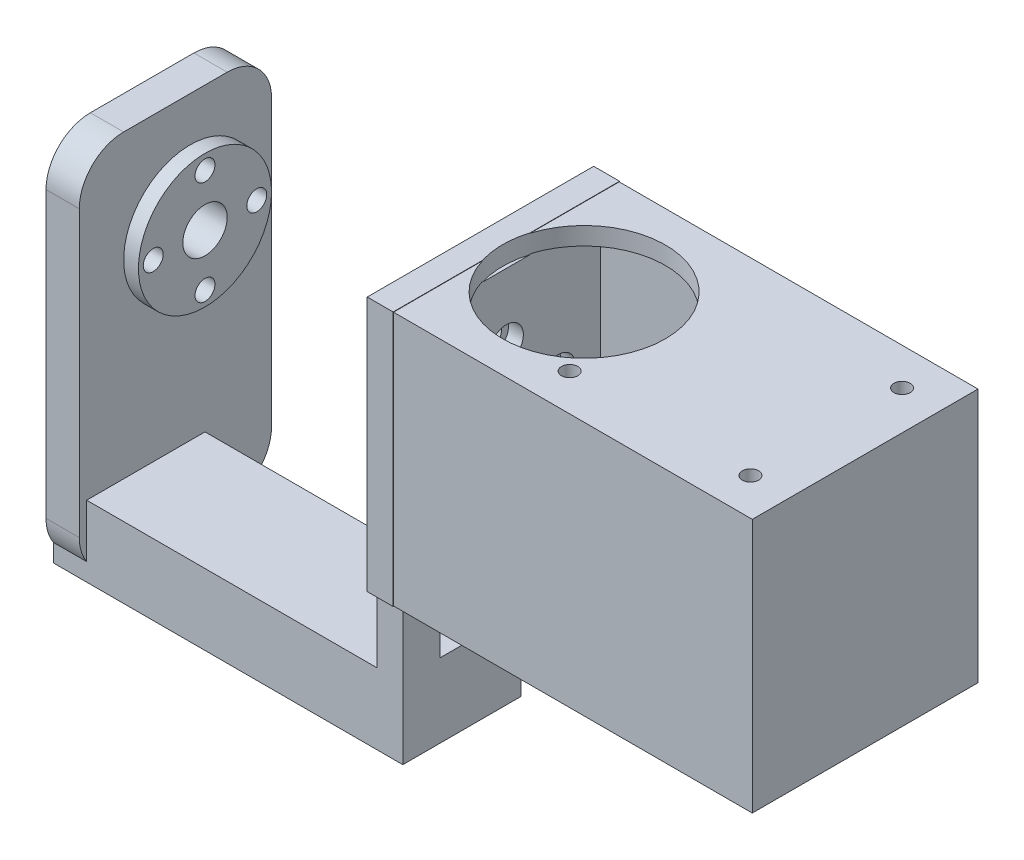
SolidWorks part; units mm, degrees
ref_plane "Front Plane" through (0, 0, 0) normal (0, 0, 1) x (1, 0, 0)
ref_plane "Top Plane" through (0, 0, 0) normal (0, 1, 0) x (1, 0, 0)
ref_plane "Right Plane" through (0, 0, 0) normal (1, 0, 0) x (0, 0, -1)
ref_plane "PX_m14_010" through (-14.01, 0, 0) normal (1, 0, 0) x (0, 0, -1)
sketch "S_prism1" plane through (-14.01, 0, 0) normal (1, 0, 0) x (0, 0, -1)
  line L0 (15.31, 18.45) -> (15.31, -16.05)
  line L1 (15.31, -16.05) -> (-15.31, -16.05)
  line L2 (-15.31, -16.05) -> (-15.31, 18.45)
  line L3 (-15.31, 18.45) -> (15.31, 18.45)
extrude "Boss_1" add sketch "S_prism1" along normal blind 3.5
ref_plane "PX_m53_260" through (-53.26, 0, 0) normal (1, 0, 0) x (0, 0, -1)
sketch "S_cyl2" plane through (-53.26, 0, 0) normal (1, 0, 0) x (0, 0, -1)
  circle A0 centre (0, 0) radius 9
  dimension "D1_S_cyl2" = 18
extrude "Boss_2" add sketch "S_cyl2" along normal blind 2
ref_plane "PX_m57_760" through (-57.76, 0, 0) normal (1, 0, 0) x (0, 0, -1)
sketch "S_prism3" plane through (-57.76, 0, 0) normal (1, 0, 0) x (0, 0, -1)
  line L0 (11, 9) -> (11, -29.5)
  line L1 (5, -35.5) -> (-9, -35.5)
  line L2 (-15, -29.5) -> (-15, 9)
  line L3 (-9, 15) -> (5, 15)
  arc A0 (5, 15) -> (11, 9) centre (4.9999, 8.9999) cw
  arc A1 (11, -29.5) -> (5, -35.5) centre (4.9999, -29.4999) cw
  arc A2 (-9, -35.5) -> (-15, -29.5) centre (-8.9999, -29.4999) cw
  arc A3 (-15, 9) -> (-9, 15) centre (-8.9999, 8.9999) cw
extrude "Boss_3" add sketch "S_prism3" along normal blind 4.5
ref_plane "PZ_m15_260" through (0, 0, -15.26) normal (0, 0, 1) x (1, 0, 0)
sketch "S_box4" plane through (0, 0, -15.26) normal (0, 0, 1) x (1, 0, 0)
  line L0 (-13.01, -16) -> (-10.51, -16)
  line L1 (-10.51, -16) -> (-10.51, 18.4)
  line L2 (-10.51, 18.4) -> (-13.01, 18.4)
  line L3 (-13.01, 18.4) -> (-13.01, -16)
  dimension "P1" = 13.01
  dimension "P2" = 16
  dimension "P3" = 10.51
  dimension "P4" = 16
  dimension "P5" = 10.51
  dimension "P6" = 18.4
  dimension "P7" = 13.01
  dimension "P8" = 18.4
extrude "Boss_4" add sketch "S_box4" along normal blind 30.52
sketch "S_box5" plane through (0, 0, -15.26) normal (0, 0, 1) x (1, 0, 0)
  line L0 (35.51, -16) -> (38.01, -16)
  line L1 (38.01, -16) -> (38.01, 18.4)
  line L2 (38.01, 18.4) -> (35.51, 18.4)
  line L3 (35.51, 18.4) -> (35.51, -16)
  dimension "P1" = 35.51
  dimension "P2" = 16
  dimension "P3" = 38.01
  dimension "P4" = 16
  dimension "P5" = 38.01
  dimension "P6" = 18.4
  dimension "P7" = 35.51
  dimension "P8" = 18.4
extrude "Boss_5" add sketch "S_box5" along normal blind 30.52
sketch "S_box6" plane through (0, 0, -15.26) normal (0, 0, 1) x (1, 0, 0)
  line L0 (-13.01, -16) -> (38.01, -16)
  line L1 (38.01, -16) -> (38.01, 18.4)
  line L2 (38.01, 18.4) -> (-13.01, 18.4)
  line L3 (-13.01, 18.4) -> (-13.01, -16)
  dimension "P1" = 13.01
  dimension "P2" = 16
  dimension "P3" = 38.01
  dimension "P4" = 16
  dimension "P5" = 38.01
  dimension "P6" = 18.4
  dimension "P7" = 13.01
  dimension "P8" = 18.4
extrude "Boss_6" add sketch "S_box6" along normal blind 2.5
ref_plane "PZ_p12_760" through (0, 0, 12.76) normal (0, 0, 1) x (1, 0, 0)
sketch "S_box7" plane through (0, 0, 12.76) normal (0, 0, 1) x (1, 0, 0)
  line L0 (-13.01, -16) -> (38.01, -16)
  line L1 (38.01, -16) -> (38.01, 18.4)
  line L2 (38.01, 18.4) -> (-13.01, 18.4)
  line L3 (-13.01, 18.4) -> (-13.01, -16)
  dimension "P1" = 13.01
  dimension "P2" = 16
  dimension "P3" = 38.01
  dimension "P4" = 16
  dimension "P5" = 38.01
  dimension "P6" = 18.4
  dimension "P7" = 13.01
  dimension "P8" = 18.4
extrude "Boss_7" add sketch "S_box7" along normal blind 2.5
sketch "S_box8" plane through (0, 0, -15.26) normal (0, 0, 1) x (1, 0, 0)
  line L0 (-13.01, 16) -> (38.01, 16)
  line L1 (38.01, 16) -> (38.01, 18.4)
  line L2 (38.01, 18.4) -> (-13.01, 18.4)
  line L3 (-13.01, 18.4) -> (-13.01, 16)
  dimension "P1" = 13.01
  dimension "P2" = 16
  dimension "P3" = 38.01
  dimension "P4" = 16
  dimension "P5" = 38.01
  dimension "P6" = 18.4
  dimension "P7" = 13.01
  dimension "P8" = 18.4
extrude "Boss_8" add sketch "S_box8" along normal blind 30.52
ref_plane "PZ_p9_000" through (0, 0, 9) normal (0, 0, 1) x (1, 0, 0)
sketch "S_box9" plane through (0, 0, 9) normal (0, 0, 1) x (1, 0, 0)
  line L0 (-14.01, -25.725) -> (-10.51, -25.725)
  line L1 (-10.51, -25.725) -> (-10.51, -16)
  line L2 (-10.51, -16) -> (-14.01, -16)
  line L3 (-14.01, -16) -> (-14.01, -25.725)
  dimension "P1" = 14.01
  dimension "P2" = 25.725
  dimension "P3" = 10.51
  dimension "P4" = 25.725
  dimension "P5" = 10.51
  dimension "P6" = 16
  dimension "P7" = 14.01
  dimension "P8" = 16
extrude "Boss_9" add sketch "S_box9" along normal blind 5
ref_plane "PZ_m2_000" through (0, 0, -2) normal (0, 0, 1) x (1, 0, 0)
sketch "S_box10" plane through (0, 0, -2) normal (0, 0, 1) x (1, 0, 0)
  line L0 (-14.01, -35.225) -> (-10.51, -35.225)
  line L1 (-10.51, -35.225) -> (-10.51, -25.225)
  line L2 (-10.51, -25.225) -> (-14.01, -25.225)
  line L3 (-14.01, -25.225) -> (-14.01, -35.225)
  dimension "P1" = 14.01
  dimension "P2" = 35.225
  dimension "P3" = 10.51
  dimension "P4" = 35.225
  dimension "P5" = 10.51
  dimension "P6" = 25.225
  dimension "P7" = 14.01
  dimension "P8" = 25.225
extrude "Boss_10" add sketch "S_box10" along normal blind 16
sketch "S_box11" plane through (0, 0, -2) normal (0, 0, 1) x (1, 0, 0)
  line L0 (-57.76, -35.225) -> (-10.51, -35.225)
  line L1 (-10.51, -35.225) -> (-10.51, -25.625)
  line L2 (-10.51, -25.625) -> (-57.76, -25.625)
  line L3 (-57.76, -25.625) -> (-57.76, -35.225)
  dimension "P1" = 57.76
  dimension "P2" = 35.225
  dimension "P3" = 10.51
  dimension "P4" = 35.225
  dimension "P5" = 10.51
  dimension "P6" = 25.625
  dimension "P7" = 57.76
  dimension "P8" = 25.625
extrude "Boss_11" add sketch "S_box11" along normal blind 16
ref_plane "PX_m14_110" through (-14.11, 0, 0) normal (1, 0, 0) x (0, 0, -1)
sketch "S_hole12" plane through (-14.11, 0, 0) normal (1, 0, 0) x (0, 0, -1)
  circle A0 centre (0, 0) radius 3
  dimension "D1_S_hole12" = 6
extrude "Hole_12" cut sketch "S_hole12" along normal blind 3.7
sketch "S_hole13" plane through (-14.11, 0, 0) normal (1, 0, 0) x (0, 0, -1)
  circle A0 centre (0, -7) radius 1.35
  dimension "D1_S_hole13" = 2.7
  dimension "P2" = 7
extrude "Hole_13" cut sketch "S_hole13" along normal blind 3.7
sketch "S_hole14" plane through (-14.11, 0, 0) normal (1, 0, 0) x (0, 0, -1)
  circle A0 centre (-7, 0) radius 1.35
  dimension "D1_S_hole14" = 2.7
  dimension "P2" = 7
extrude "Hole_14" cut sketch "S_hole14" along normal blind 3.7
sketch "S_hole15" plane through (-14.11, 0, 0) normal (1, 0, 0) x (0, 0, -1)
  circle A0 centre (0, 7) radius 1.35
  dimension "D1_S_hole15" = 2.7
  dimension "P2" = 7
extrude "Hole_15" cut sketch "S_hole15" along normal blind 3.7
sketch "S_hole16" plane through (-14.11, 0, 0) normal (1, 0, 0) x (0, 0, -1)
  circle A0 centre (7, 0) radius 1.35
  dimension "D1_S_hole16" = 2.7
  dimension "P2" = 7
extrude "Hole_16" cut sketch "S_hole16" along normal blind 3.7
ref_plane "PX_m57_860" through (-57.86, 0, 0) normal (1, 0, 0) x (0, 0, -1)
sketch "S_hole17" plane through (-57.86, 0, 0) normal (1, 0, 0) x (0, 0, -1)
  circle A0 centre (0, 0) radius 3
  dimension "D1_S_hole17" = 6
extrude "Hole_17" cut sketch "S_hole17" along normal blind 6.7
sketch "S_hole18" plane through (-57.86, 0, 0) normal (1, 0, 0) x (0, 0, -1)
  circle A0 centre (0, -7) radius 1.35
  dimension "D1_S_hole18" = 2.7
  dimension "P2" = 7
extrude "Hole_18" cut sketch "S_hole18" along normal blind 6.7
sketch "S_hole19" plane through (-57.86, 0, 0) normal (1, 0, 0) x (0, 0, -1)
  circle A0 centre (-7, 0) radius 1.35
  dimension "D1_S_hole19" = 2.7
  dimension "P2" = 7
extrude "Hole_19" cut sketch "S_hole19" along normal blind 6.7
sketch "S_hole20" plane through (-57.86, 0, 0) normal (1, 0, 0) x (0, 0, -1)
  circle A0 centre (0, 7) radius 1.35
  dimension "D1_S_hole20" = 2.7
  dimension "P2" = 7
extrude "Hole_20" cut sketch "S_hole20" along normal blind 6.7
sketch "S_hole21" plane through (-57.86, 0, 0) normal (1, 0, 0) x (0, 0, -1)
  circle A0 centre (7, 0) radius 1.35
  dimension "D1_S_hole21" = 2.7
  dimension "P2" = 7
extrude "Hole_21" cut sketch "S_hole21" along normal blind 6.7
ref_plane "PY_p15_900" through (0, 15.9, 0) normal (0, 1, 0) x (1, 0, 0)
sketch "S_hole22" plane through (0, 15.9, 0) normal (0, 1, 0) x (1, 0, 0)
  circle A0 centre (0, 0) radius 11
  dimension "D1_S_hole22" = 22
extrude "Hole_22" cut sketch "S_hole22" along normal blind 2.6
sketch "S_hole23" plane through (0, 15.9, 0) normal (0, 1, 0) x (1, 0, 0)
  circle A0 centre (8.3, -10.25) radius 1.1
  dimension "D1_S_hole23" = 2.2
  dimension "P2" = 8.3
  dimension "P3" = 10.25
extrude "Hole_23" cut sketch "S_hole23" along normal blind 2.6
sketch "S_hole24" plane through (0, 15.9, 0) normal (0, 1, 0) x (1, 0, 0)
  circle A0 centre (32.75, 10.25) radius 1.1
  dimension "D1_S_hole24" = 2.2
  dimension "P2" = 32.75
  dimension "P3" = 10.25
extrude "Hole_24" cut sketch "S_hole24" along normal blind 2.6
sketch "S_hole25" plane through (0, 15.9, 0) normal (0, 1, 0) x (1, 0, 0)
  circle A0 centre (32.75, -10.25) radius 1.1
  dimension "D1_S_hole25" = 2.2
  dimension "P2" = 32.75
  dimension "P3" = 10.25
extrude "Hole_25" cut sketch "S_hole25" along normal blind 2.6
ref_plane "PX_m12_510" through (-12.51, 0, 0) normal (1, 0, 0) x (0, 0, -1)
sketch "S_hole26" plane through (-12.51, 0, 0) normal (1, 0, 0) x (0, 0, -1)
  circle A0 centre (0, -7) radius 2.3
  dimension "D1_S_hole26" = 4.6
  dimension "P2" = 7
extrude "Hole_26" cut sketch "S_hole26" along normal blind 2.1
sketch "S_hole27" plane through (-12.51, 0, 0) normal (1, 0, 0) x (0, 0, -1)
  circle A0 centre (-7, 0) radius 2.3
  dimension "D1_S_hole27" = 4.6
  dimension "P2" = 7
extrude "Hole_27" cut sketch "S_hole27" along normal blind 2.1
sketch "S_hole28" plane through (-12.51, 0, 0) normal (1, 0, 0) x (0, 0, -1)
  circle A0 centre (0, 7) radius 2.3
  dimension "D1_S_hole28" = 4.6
  dimension "P2" = 7
extrude "Hole_28" cut sketch "S_hole28" along normal blind 2.1
sketch "S_hole29" plane through (-12.51, 0, 0) normal (1, 0, 0) x (0, 0, -1)
  circle A0 centre (7, 0) radius 2.3
  dimension "D1_S_hole29" = 4.6
  dimension "P2" = 7
extrude "Hole_29" cut sketch "S_hole29" along normal blind 2.1
equation "\"plate_t\" = 3"
equation "\"clearance\" = 0.4"
